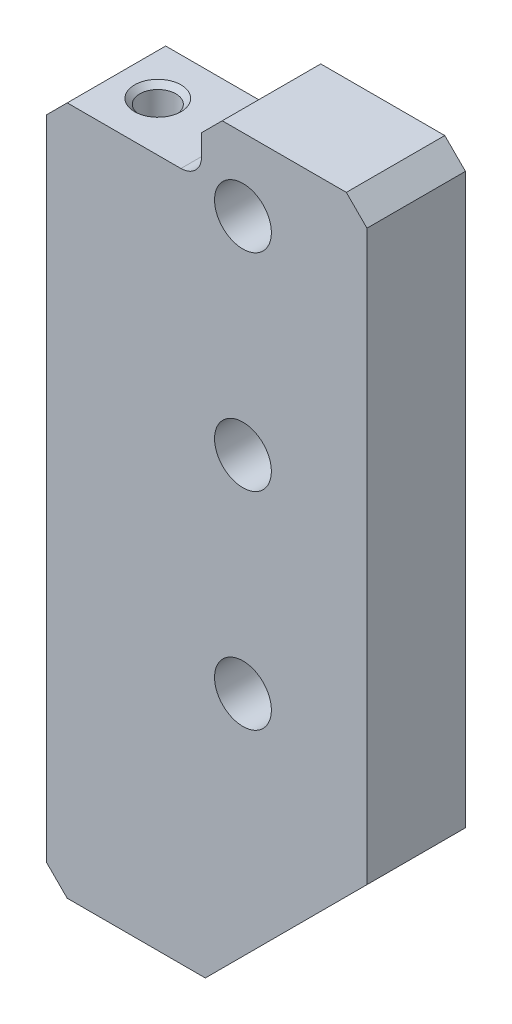
SolidWorks part; units mm, degrees
material "Plain Carbon Steel"
ref_plane "Front Plane" through (0, 0, 0) normal (0, 0, 1) x (1, 0, 0)
ref_plane "Top Plane" through (0, 0, 0) normal (0, 1, 0) x (1, 0, 0)
ref_plane "Right Plane" through (0, 0, 0) normal (1, 0, 0) x (0, 0, -1)
sketch "Sketch1" plane through (0, 0, 0) normal (0, 0, 1) x (1, 0, 0)
  line L0 (-160.8878, 18.5523) -> (-176.2477, 18.5523) construction
  line L1 (-176.2477, 85.1924) -> (-176.2477, 18.5523) construction
  line L2 (-176.2477, 85.1924) -> (-161.2477, 85.1924) construction
  line L3 (-161.2477, 85.1924) -> (-161.2477, 91.1924) construction
  line L4 (-161.2477, 91.1924) -> (-145.2477, 91.1924) construction
  line L5 (-145.2477, 91.1924) -> (-145.2477, 34.1924) construction
  line L6 (-145.2477, 34.1924) -> (-160.8878, 18.5523) construction
  line L7 (-168.7477, 96.1924) -> (-168.7477, 85.1924) construction
  line L8 (-170.2477, 96.1924) -> (-170.2477, 85.1924) construction
  line L9 (-171.7477, 96.1924) -> (-171.7477, 85.1924) construction
  line L10 (-160.8878, 18.5523) -> (-176.2477, 18.5523)
  line L11 (-176.2477, 85.1924) -> (-176.2477, 18.5523)
  line L12 (-176.2477, 85.1924) -> (-161.2477, 85.1924)
  line L13 (-161.2477, 85.1924) -> (-161.2477, 91.1924)
  line L14 (-161.2477, 91.1924) -> (-145.2477, 91.1924)
  line L15 (-145.2477, 91.1924) -> (-145.2477, 34.1924)
  line L16 (-145.2477, 34.1924) -> (-160.8878, 18.5523)
  line L17 (-168.7477, 96.1924) -> (-168.7477, 85.1924) construction
  line L18 (-170.2477, 96.1924) -> (-170.2477, 85.1924) construction
  line L19 (-171.7477, 96.1924) -> (-171.7477, 85.1924) construction
  line L20 (-168.7477, 85.1924) -> (-168.7477, 65.1924) construction
  line L21 (-168.7477, 65.1924) -> (-170.2477, 64.3264) construction
  line L22 (-170.2477, 64.3264) -> (-171.7477, 65.1924) construction
  line L23 (-171.7477, 65.1924) -> (-171.7477, 85.1924) construction
  line L24 (-168.7477, 65.1924) -> (-171.7477, 65.1924) construction
  circle A0 centre (-157.2477, 44.1924) radius 2.75 construction
  circle A1 centre (-157.2477, 64.1924) radius 2.75 construction
  circle A2 centre (-157.2477, 84.1924) radius 2.75 construction
  circle A3 centre (-169.2477, 84.1924) radius 2.75 construction
  circle A4 centre (-157.2477, 44.1924) radius 2.75
  circle A5 centre (-157.2477, 64.1924) radius 2.75
  circle A6 centre (-157.2477, 84.1924) radius 2.75
  circle A7 centre (-169.2477, 84.1924) radius 2.75 construction
  dimension "D1" = 120
  dimension "D2" = 20
extrude "Boss-Extrude1" add sketch "Sketch1" along normal blind 4.7625 and the other way blind 4.7625
sketch "Sketch2" plane through (0, 0, 0) normal (0, 0, 1) x (1, 0, 0)
  line L0 (-170.2477, 85.1924) -> (-171.9977, 85.1924)
  line L1 (-171.9977, 85.1924) -> (-171.9977, 80.1924)
  line L2 (-171.9977, 80.1924) -> (-171.4477, 79.8748)
  line L3 (-171.4477, 79.8748) -> (-171.4477, 65.0192)
  line L4 (-171.4477, 65.0192) -> (-170.2477, 64.3264)
  line L5 (-170.2477, 85.1924) -> (-170.2477, 64.3264)
  line L6 (-161.2477, 85.1924) -> (-176.2477, 85.1924) construction
  line L7 (-170.2477, 85.1924) -> (-170.2477, 95.5113) construction
  line L8 (-176.2477, 85.1924) -> (-161.2477, 85.1924) construction
  line L9 (-170.2477, 96.1924) -> (-170.2477, 85.1924) construction
  line L10 (-170.2477, 64.3264) -> (-171.7477, 65.1924) construction
  dimension "D1" = 3.5
  dimension "D2" = 5
  dimension "D3" = 2.4
revolve "Cut-Revolve1" cut sketch "Sketch2" angle 360 about L7
chamfer "Chamfer1" distance 2 angle 45 4 edges at (-176.2477, 18.5523, 0) (-145.2477, 91.1924, 0) (-161.2477, 91.1924, 0) (-176.2477, 85.1924, 0)
chamfer "Chamfer2" distance 0.5 angle 45 1 edges at (-170.2477, 85.1924, -1.75)
fillet "Fillet1" radius 2 1 edges at (-161.2477, 85.1924, 0)
